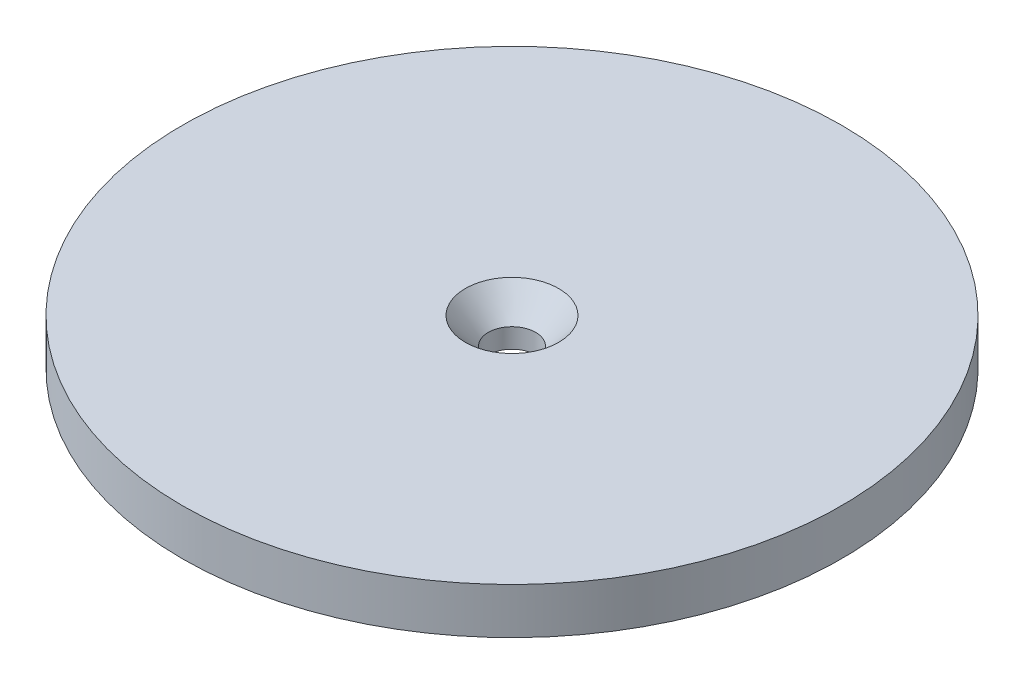
SolidWorks part; units mm, degrees
ref_plane "Front Plane" through (0, 0, 0) normal (0, 0, 1) x (1, 0, 0)
ref_plane "Top Plane" through (0, 0, 0) normal (0, 1, 0) x (1, 0, 0)
ref_plane "Right Plane" through (0, 0, 0) normal (1, 0, 0) x (0, 0, -1)
sketch "Sketch1" plane through (0, 0, 0) normal (0, 1, 0) x (1, 0, 0)
  circle A0 centre (0, 0) radius 20.066 construction
  circle A1 centre (0, 0) radius 45.466
  dimension "D1" = 25.4
extrude "Boss-Extrude1" add sketch "Sketch1" along normal blind 25.4
sketch "Sketch3" plane through (0, 0, 0) normal (0, -1, 0) x (1, 0, 0)
  circle A0 centre (0, 0) radius 20.32
hole_wizard "CSK for 1/4 Flat Head Machine Screw1" positions "Sketch6" profile "Sketch7" countersink size "1/4" standard "ANSI Inch"
sketch "Sketch6" plane through (0, 25.4, 0) normal (0, 1, 0) x (1, 0, 0)
  point P0 (0, 0)
sketch "Sketch7" plane through (0, 25.4, 0) normal (1, 0, 0) x (0, 0, 1)
  line L0 (0, 0) -> (0, 27.3611)
  line L1 (0, 27.3611) -> (3.2639, 25.4)
  line L2 (3.2639, 25.4) -> (3.2639, 3.6524)
  line L3 (3.2639, 3.6524) -> (6.4389, 0)
  line L5 (6.4389, 0) -> (0, 0)
  line L6 (-3.2639, 3.6524) -> (-6.4389, 0) construction
  line L10 (0, 27.3611) -> (-3.2639, 25.4) construction
  line L11 (0, -6.35) -> (0, 107.95) construction
  dimension "Hole Dia." = 6.5278
  dimension "Hole Depth" = 25.4
  dimension "Near C'Sink Dia." = 12.8778
  dimension "Near C'Sink Angle" = 82
  dimension "Drill Angle" = 118
sketch "Sketch9" plane through (0, 0, 0) normal (0, -1, 0) x (1, 0, 0)
  circle A0 centre (0, 0) radius 53.0319
extrude "Cut-Extrude3" cut sketch "Sketch9" against normal blind 12.7
sketch "Sketch11" plane through (0, 12.7, 0) normal (0, -1, 0) x (1, 0, 0)
  circle A0 centre (0, 0) radius 48.964
extrude "Cut-Extrude4" cut sketch "Sketch11" against normal blind 6.35
